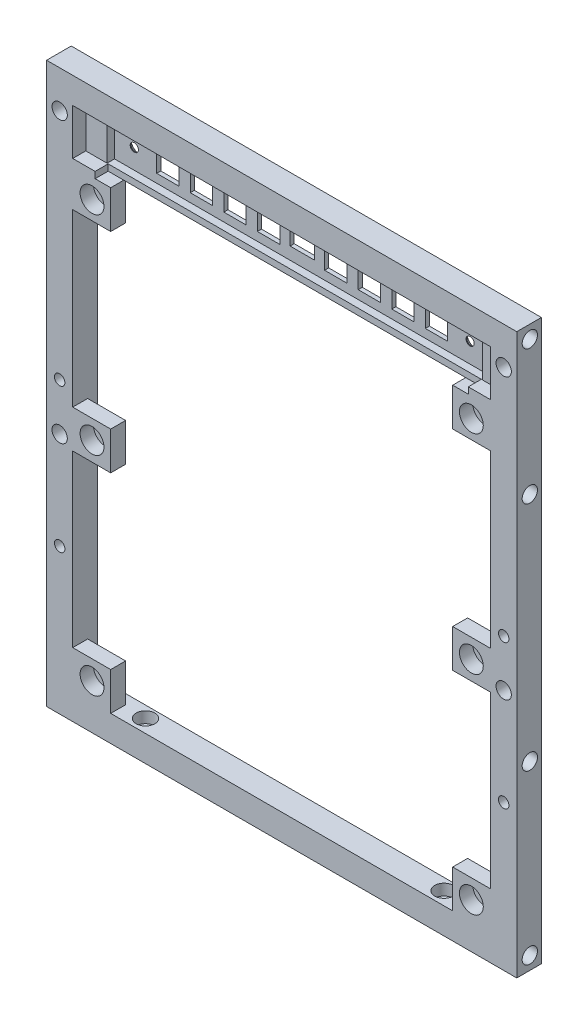
SolidWorks part; units mm, degrees
ref_plane "Front Plane" through (0, 0, 0) normal (0, 0, 1) x (1, 0, 0)
ref_plane "Top Plane" through (0, 0, 0) normal (0, 1, 0) x (1, 0, 0)
ref_plane "Right Plane" through (0, 0, 0) normal (1, 0, 0) x (0, 0, -1)
sketch "Sketch1" plane through (0, 0, 0) normal (0, 0, 1) x (1, 0, 0)
  line L1 (-63, -75) -> (63, -75)
  line L2 (-63, -75) -> (-63, 75)
  line L3 (-63, 75) -> (63, 75)
  line L4 (63, -75) -> (63, 75)
  line L5 (-63, -75) -> (63, 75) construction
  line L6 (-63, 75) -> (63, -75) construction
  line L7 (-56, -68) -> (56, -68)
  line L8 (-56, -68) -> (-56, 68)
  line L9 (-56, 68) -> (56, 68)
  line L10 (56, -68) -> (56, 68)
  line L11 (-56, -68) -> (56, 68) construction
  line L12 (-56, 68) -> (56, -68) construction
  point P0 (0, 0)
  point P6 (0, 0)
  dimension "D1" = 126
  dimension "D2" = 150
  dimension "D3" = 7
  dimension "D4" = 7
extrude "Boss-Extrude1" add sketch "Sketch1" along normal blind 7
sketch "Sketch2" plane through (-63, 0, 0) normal (-1, 0, 0) x (0, 0, 1)
  line L0 (3.5, 71.5) -> (3.5, -71.5) construction
  line L1 (7, 75) -> (0, 75) construction
  circle A0 centre (3.5, -71.5) radius 2.05
  circle A2 centre (3.5, 71.5) radius 2.05
  circle A3 centre (3.5, 35.5) radius 2.05
  circle A4 centre (3.5, -26.5) radius 2.05
  point P2 (3.5, 0)
  point P7 (3.5, 75)
  dimension "D2" = 4.1
  dimension "D3" = 36
  dimension "D4" = 45
  dimension "D1" = 3.5
extrude "Cut-Extrude1" cut sketch "Sketch2" against normal blind 6
mirror "Mirror1" about plane through (0, 0, 0) normal (1, 0, 0) of "Cut-Extrude1"
sketch "Sketch3" plane through (0, -68, 0) normal (0, 1, 0) x (1, 0, 0)
  line L0 (0, 0) -> (0, -7) construction
  line L1 (-56, 0) -> (56, 0) construction
  line L2 (-56, -7) -> (56, -7) construction
  line L3 (40, -3.5) -> (-40, -3.5) construction
  circle A0 centre (40, -3.5) radius 1.35
  circle A1 centre (-40, -3.5) radius 1.35
  point P9 (0, -3.5)
  dimension "D1" = 2.7
  dimension "D2" = 80
extrude "Cut-Extrude2" cut sketch "Sketch3" against normal through all
sketch "Sketch4" plane through (0, -68, 0) normal (0, 1, 0) x (1, 0, 0)
  circle A0 centre (40, -3.5) radius 2.5
  circle A1 centre (-40, -3.5) radius 2.5
  dimension "D1" = 5
extrude "Cut-Extrude3" cut sketch "Sketch4" against normal blind 3
sketch "Sketch5" plane through (0, 0, 0) normal (0, 0, -1) x (-1, 0, 0)
  line L0 (-59.5, -75) -> (-59.5, 75) construction
  line L1 (63, -75) -> (-63, -75) construction
  line L2 (-63, 75) -> (63, 75) construction
  line L3 (-56, 0) -> (-63, 0) construction
  line L4 (-56, -68) -> (-56, 68) construction
  line L5 (-63, -75) -> (-63, 75) construction
  line L6 (0, 75) -> (0, -75) construction
  line L7 (56, -68) -> (-56, -68) construction
  circle A0 centre (-59.5, 2.6) radius 1.4
  circle A1 centre (59.5, 2.6) radius 1.4
  circle A2 centre (-59.5, -36) radius 1.4
  circle A3 centre (59.5, -36) radius 1.4
  point P12 (-59.5, 0)
  point P13 (-59.5, 0)
  dimension "D1" = 2.8
  dimension "D2" = 2.6
  dimension "D3" = 32
extrude "Cut-Extrude4" cut sketch "Sketch5" against normal through all
sketch "Sketch6" plane through (0, 0, 0) normal (0, 0, -1) x (-1, 0, 0)
  circle A0 centre (-59.5, 2.6) radius 2.5
  circle A1 centre (59.5, 2.6) radius 2.5
  circle A2 centre (-59.5, -36) radius 2.5
  circle A3 centre (59.5, -36) radius 2.5
  dimension "D1" = 5
extrude "Cut-Extrude5" cut sketch "Sketch6" against normal blind 3
sketch "Sketch7" plane through (0, 0, 0) normal (0, 0, -1) x (-1, 0, 0)
  line L0 (-56, 68) -> (-63, 68) construction
  line L1 (-63, -75) -> (-63, 75) construction
  line L2 (-59.5, 65) -> (-59.5, -10) construction
  line L3 (-63, 75) -> (63, 75) construction
  circle A0 centre (-59.5, 65) radius 2.05
  circle A1 centre (-59.5, -10) radius 2.05
  point P8 (-59.5, 68)
  dimension "D1" = 4.1
  dimension "D2" = 10
  dimension "D3" = 75
extrude "Cut-Extrude6" cut sketch "Sketch7" against normal through all
mirror "Mirror2" about plane through (0, 0, 0) normal (1, 0, 0) of "Cut-Extrude6"
sketch "Sketch8" plane through (0, 0, 3) normal (0, 0, -1) x (-1, 0, 0)
  line L2 (-60.9, 0.5288) -> (-60.9, 4.6712)
  line L4 (-58.1, 0.5288) -> (-58.1, 4.6712)
  line L5 (-60.9, 0.5288) -> (-58.1, 4.6712) construction
  line L6 (-60.9, 4.6712) -> (-58.1, 0.5288) construction
  line L8 (-60.9, -38.0712) -> (-60.9, -33.9288)
  line L10 (-58.1, -38.0712) -> (-58.1, -33.9288)
  line L11 (-60.9, -38.0712) -> (-58.1, -33.9288) construction
  line L12 (-60.9, -33.9288) -> (-58.1, -38.0712) construction
  circle A0 centre (-59.5, 2.6) radius 2.5 construction
  circle A1 centre (-59.5, -36) radius 2.5 construction
  circle A2 centre (-59.5, -36) radius 2.5 construction
  arc A3 (-58.1, 4.6712) -> (-60.9, 4.6712) centre (-59.5, 2.6) ccw
  arc A4 (-58.1, -33.9288) -> (-60.9, -33.9288) centre (-59.5, -36) ccw
  circle A5 centre (-59.5, 2.6) radius 1.4 construction
  circle A6 centre (-59.5, -36) radius 1.4 construction
  arc A7 (-60.9, -38.0712) -> (-58.1, -38.0712) centre (-59.5, -36) ccw
  arc A8 (-60.9, 0.5288) -> (-58.1, 0.5288) centre (-59.5, 2.6) ccw
  point P0 (-59.5, 2.6)
  point P8 (-59.5, -36)
extrude "Cut-Extrude7" cut sketch "Sketch8" against normal blind 0.2
sketch "Sketch9" plane through (0, 0, 3.2) normal (0, 0, -1) x (-1, 0, 0)
  line L0 (-58.1, 2.6) -> (-58.1, 4.6712) construction
  line L1 (-60.9, 1.2) -> (-58.1, 1.2)
  line L2 (-60.9, 1.2) -> (-60.9, 4)
  line L3 (-60.9, 4) -> (-58.1, 4)
  line L4 (-58.1, 1.2) -> (-58.1, 4)
  line L5 (-60.9, 1.2) -> (-58.1, 4) construction
  line L6 (-60.9, 4) -> (-58.1, 1.2) construction
  line L7 (-58.1, -38.0712) -> (-58.1, -33.9288) construction
  line L8 (-60.9, -37.4) -> (-58.1, -37.4)
  line L9 (-60.9, -37.4) -> (-60.9, -34.6)
  line L10 (-60.9, -34.6) -> (-58.1, -34.6)
  line L11 (-58.1, -37.4) -> (-58.1, -34.6)
  line L12 (-60.9, -37.4) -> (-58.1, -34.6) construction
  line L13 (-60.9, -34.6) -> (-58.1, -37.4) construction
  arc A0 (-58.1, 2.6) -> (-60.9, 2.6) centre (-59.5, 2.6) ccw construction
  point P0 (-59.5, 2.6)
  point P8 (-59.5, -36)
extrude "Cut-Extrude8" cut sketch "Sketch9" against normal blind 0.2
mirror "Mirror3" about plane through (0, 0, 0) normal (1, 0, 0) of "Cut-Extrude8", "Cut-Extrude7"
sketch "Sketch10" plane through (0, 0, 7) normal (0, 0, 1) x (1, 0, 0)
  line L0 (56, -68) -> (56, 68) construction
  line L1 (56, -68) -> (50, -68)
  line L2 (56, -68) -> (56, -62)
  line L3 (56, -62) -> (50, -62)
  line L4 (50, -68) -> (50, -62)
  line L5 (56, -38.5) -> (50, -38.5)
  line L6 (56, -38.5) -> (56, -32.5)
  line L7 (56, -32.5) -> (50, -32.5)
  line L8 (50, -38.5) -> (50, -32.5)
  line L9 (-56, -68) -> (56, -68) construction
  dimension "D1" = 6
  dimension "D2" = 35.5
extrude "Boss-Extrude2" add sketch "Sketch10" against normal offset from surface (5.5 mm away) 1.5 up to face at (-57.45, -10, 0)
sketch "Sketch11" plane through (0, 0, 1.5) normal (0, 0, -1) x (-1, 0, 0)
  line L0 (-56, -38.5) -> (-50, -32.5) construction
  line L2 (-56, -68) -> (-50, -62) construction
  circle A0 centre (-53, -35.5) radius 1.65
  circle A1 centre (-53, -65) radius 1.65
  dimension "D1" = 3.3
extrude "Cut-Extrude9" cut sketch "Sketch11" against normal through all
mirror "Mirror4" about plane through (0, 0, 0) normal (1, 0, 0) of "Cut-Extrude9", "Boss-Extrude2"
sketch "Sketch12" plane through (0, 0, 0) normal (0, 0, -1) x (-1, 0, 0)
  line L0 (56, 68) -> (56, -68) construction
  line L1 (-56, 68) -> (56, 68)
  line L2 (-56, 68) -> (-56, 54)
  line L3 (-56, 54) -> (56, 54)
  line L4 (56, 68) -> (56, 54)
  dimension "D1" = 14
extrude "Boss-Extrude3" add sketch "Sketch12" against normal blind 1.5
sketch "Sketch13" plane through (0, 0, 1.5) normal (0, 0, 1) x (1, 0, 0)
  line L0 (-56, 68) -> (56, 54) construction
  line L2 (-50.3, 55.7) -> (50.3, 55.7)
  line L3 (-50.3, 55.7) -> (-50.3, 66.3)
  line L4 (-50.3, 66.3) -> (50.3, 66.3)
  line L5 (50.3, 55.7) -> (50.3, 66.3)
  line L6 (-50.3, 55.7) -> (50.3, 66.3) construction
  line L7 (-50.3, 66.3) -> (50.3, 55.7) construction
  line L8 (-56, 54) -> (56, 54)
  line L9 (-56, 54) -> (-56, 68)
  line L10 (-56, 68) -> (56, 68)
  line L11 (56, 54) -> (56, 68)
  line L12 (-56, 54) -> (56, 68) construction
  line L13 (-56, 68) -> (56, 54) construction
  point P4 (0, 61)
  point P9 (0, 61)
  dimension "D1" = 100.6
  dimension "D2" = 10.6
extrude "Boss-Extrude4" add sketch "Sketch13" along normal blind 2
sketch "Sketch14" plane through (0, 0, 1.5) normal (0, 0, 1) x (1, 0, 0)
  line L0 (0, 66.3) -> (0, 55.7) construction
  line L1 (50.3, 66.3) -> (-50.3, 66.3) construction
  line L2 (-50.3, 55.7) -> (50.3, 55.7) construction
  line L3 (-50.3, 61) -> (50.3, 61) construction
  line L4 (50.3, 55.7) -> (50.3, 66.3) construction
  line L5 (-33, 64) -> (-39, 64)
  line L6 (-3.25, 59) -> (3.25, 59)
  line L7 (-3.25, 59) -> (-3.25, 63)
  line L8 (-3.25, 63) -> (3.25, 63)
  line L9 (3.25, 59) -> (3.25, 63)
  line L10 (-3.25, 59) -> (3.25, 63) construction
  line L11 (-3.25, 63) -> (3.25, 59) construction
  line L12 (6, 58) -> (12, 58)
  line L13 (6, 58) -> (6, 64)
  line L14 (6, 64) -> (12, 64)
  line L15 (12, 58) -> (12, 64)
  line L16 (6, 58) -> (12, 64) construction
  line L17 (6, 64) -> (12, 58) construction
  line L18 (15, 58) -> (21, 58)
  line L19 (15, 58) -> (15, 64)
  line L20 (15, 64) -> (21, 64)
  line L21 (21, 58) -> (21, 64)
  line L22 (15, 58) -> (21, 64) construction
  line L23 (15, 64) -> (21, 58) construction
  line L24 (24, 58) -> (30, 58)
  line L25 (24, 58) -> (24, 64)
  line L26 (24, 64) -> (30, 64)
  line L27 (30, 58) -> (30, 64)
  line L28 (24, 58) -> (30, 64) construction
  line L29 (24, 64) -> (30, 58) construction
  line L30 (33, 58) -> (39, 58)
  line L31 (33, 58) -> (33, 64)
  line L32 (33, 64) -> (39, 64)
  line L33 (39, 58) -> (39, 64)
  line L34 (33, 58) -> (39, 64) construction
  line L35 (33, 64) -> (39, 58) construction
  line L36 (-39, 58) -> (-39, 64)
  line L37 (-33, 58) -> (-39, 58)
  line L38 (-33, 58) -> (-33, 64)
  line L39 (-24, 64) -> (-30, 64)
  line L40 (-30, 58) -> (-30, 64)
  line L41 (-24, 58) -> (-30, 58)
  line L42 (-24, 58) -> (-24, 64)
  line L43 (-15, 64) -> (-21, 64)
  line L44 (-21, 58) -> (-21, 64)
  line L45 (-15, 58) -> (-21, 58)
  line L46 (-15, 58) -> (-15, 64)
  line L47 (-6, 64) -> (-12, 64)
  line L48 (-12, 58) -> (-12, 64)
  line L49 (-6, 58) -> (-12, 58)
  line L50 (-6, 58) -> (-6, 64)
  circle A0 centre (-45, 61) radius 1.3 construction
  circle A1 centre (45, 61) radius 1.3 construction
  point P6 (0, 61)
  point P11 (0, 61)
  point P16 (9, 61)
  point P21 (18, 61)
  point P26 (27, 61)
  point P31 (36, 61)
  dimension "D10" = 2.6
  dimension "D9" = 45
  dimension "D1" = 6.5
  dimension "D2" = 4
  dimension "D3" = 6
  dimension "D4" = 9
  dimension "D5" = 9
  dimension "D6" = 9
  dimension "D7" = 9
  dimension "D8" = 45
extrude "Cut-Extrude10" cut sketch "Sketch14" against normal through all
sketch "Sketch15" plane through (0, 0, 1.5) normal (0, 0, 1) x (1, 0, 0)
  circle A0 centre (-45, 61) radius 1
  circle A1 centre (45, 61) radius 1
  dimension "D1" = 2
extrude "Boss-Extrude5" add sketch "Sketch15" along normal up to surface (2 mm away) up to face at (0, 61, 3.5)
chamfer "Chamfer1" distance 0.4 angle 45 3 edges at (-56, -7, 0) (56, -7, 0) (0, -68, 0) tangent propagation no
chamfer "Chamfer2" distance 0.4 angle 45 4 edges at (0, 75, 0) (-63, 0, 0) (0, -75, 0) (63, 0, 0)
chamfer "Chamfer3" distance 0.4 angle 45 36 edges at (-36, 58, 0) (-39, 61, 0) (-36, 64, 0) (-33, 61, 0) (-27, 58, 0) (-30, 61, 0) (-27, 64, 0) (-24, 61, 0) (-18, 58, 0) (-21, 61, 0) (-18, 64, 0) (-15, 61, 0) (-9, 58, 0) (-12, 61, 0) (-9, 64, 0) (-6, 61, 0) (0, 59, 0) (-3.25, 61, 0) (0, 63, 0) (3.25, 61, 0) (9, 58, 0) (6, 61, 0) (9, 64, 0) (12, 61, 0) (18, 58, 0) (15, 61, 0) (18, 64, 0) (21, 61, 0) (36, 58, 0) (33, 61, 0) (36, 64, 0) (39, 61, 0) (27, 58, 0) (24, 61, 0) (27, 64, 0) (30, 61, 0)
sketch "Sketch16" plane through (0, 0, 7) normal (0, 0, 1) x (1, 0, 0)
  line L0 (-50, 54) -> (-50, 55.7)
  line L1 (-56, -32.5) -> (-50, -32.5)
  line L2 (-56, -32.5) -> (-56, -26.5)
  line L3 (-56, -26.5) -> (-50, -26.5)
  line L4 (-50, -32.5) -> (-50, -26.5)
  line L5 (56, -32.5) -> (50, -32.5)
  line L6 (56, -32.5) -> (56, -26.5)
  line L7 (56, -26.5) -> (50, -26.5)
  line L8 (50, -32.5) -> (50, -26.5)
  line L9 (56, 54) -> (50, 54) construction
  line L10 (56, 54) -> (56, 48)
  line L11 (56, 48) -> (50, 48)
  line L12 (50, 54) -> (50, 48)
  line L13 (-56, 54) -> (-50, 54) construction
  line L14 (-56, 54) -> (-56, 48)
  line L15 (-56, 48) -> (-50, 48)
  line L16 (-50, 54) -> (-50, 48)
  line L17 (-50.3, 55.7) -> (50.3, 55.7) construction
  line L18 (-50, 55.7) -> (-56, 55.7)
  line L19 (-56, 68) -> (-56, 54) construction
  line L20 (-56, 55.7) -> (-56, 54)
  line L21 (50, 54) -> (50, 55.7)
  line L22 (50, 55.7) -> (56, 55.7)
  line L23 (56, 54) -> (56, 68) construction
  line L24 (56, 55.7) -> (56, 54)
  dimension "D1" = 6
extrude "Boss-Extrude7" add sketch "Sketch16" against normal offset from surface (5.5 mm away) 1.5 up to face at (-36, 61, 0)
sketch "Sketch17" plane through (0, 0, 1.5) normal (0, 0, -1) x (-1, 0, 0)
  line L0 (-50, 48) -> (50, -26.5) construction
  line L1 (-50, -26.5) -> (-50, -38.5) construction
  line L2 (-53, -29.5) -> (53, -29.5) construction
  line L3 (-53, -29.5) -> (-53, 51) construction
  line L4 (-53, 51) -> (53, 51) construction
  line L5 (53, -29.5) -> (53, 51) construction
  line L6 (-53, -29.5) -> (53, 51) construction
  line L7 (-53, 51) -> (53, -29.5) construction
  line L8 (50, -26.5) -> (56, -26.5) construction
  circle A0 centre (-53, -29.5) radius 1.65
  circle A1 centre (53, -29.5) radius 1.65
  circle A2 centre (53, 51) radius 1.65
  circle A3 centre (-53, 51) radius 1.65
  point P4 (0, 10.75)
  dimension "D3" = 3.3
  dimension "D1" = 3
  dimension "D2" = 3
extrude "Cut-Extrude11" cut sketch "Sketch17" against normal through all
sketch "Sketch18" plane through (0, 0, 1.5) normal (0, 0, 1) x (1, 0, 0)
  circle A0 centre (-45, 61) radius 1.1
  circle A1 centre (45, 61) radius 1.1
  dimension "D1" = 2.2
extrude "Cut-Extrude12" cut sketch "Sketch18" against normal through all both and the other way through all
chamfer "Chamfer4" distance 1.3 angle 45 2 edges at (-43.9, 61, 0) (46.1, 61, 0)
sketch "Sketch19" plane through (0, 0, 1.5) normal (0, 0, -1) x (-1, 0, 0)
  line L1 (-56, -68) -> (56, -68)
  line L2 (-56, -68) -> (-56, 54)
  line L3 (-56, 54) -> (56, 54)
  line L4 (56, -68) -> (56, 54)
extrude "Cut-Extrude13" cut sketch "Sketch19" against normal through all
ref_plane "Plane1" through (0, 0, 3) normal (0, 0, 1) x (1, 0, 0)
sketch "Sketch20" plane through (0, 0, 3) normal (0, 0, 1) x (1, 0, 0)
  line L0 (56, 54) -> (56, -68) construction
  line L1 (56, -68) -> (48, -68)
  line L2 (56, -68) -> (56, -60)
  line L3 (56, -60) -> (48, -60)
  line L4 (48, -68) -> (48, -60)
  line L5 (56, 54) -> (48, 54)
  line L6 (56, 54) -> (56, 46)
  line L7 (56, 46) -> (48, 46)
  line L8 (48, 54) -> (48, 46)
  line L9 (56, -24.5) -> (48, -24.5)
  line L10 (56, -24.5) -> (56, -32.5)
  line L11 (56, -32.5) -> (48, -32.5)
  line L12 (48, -24.5) -> (48, -32.5)
  dimension "D1" = 8
  dimension "D2" = 27.5
extrude "Boss-Extrude8" add sketch "Sketch20" along normal blind 7
sketch "Sketch21" plane through (0, 0, 3) normal (0, 0, -1) x (-1, 0, 0)
  line L0 (-48, 54) -> (-56, 46) construction
  line L1 (-56, -60) -> (-48, -68) construction
  line L2 (-56, -24.5) -> (-48, -32.5) construction
  circle A0 centre (-52, 50) radius 2.1
  circle A1 centre (-52, -64) radius 2.1
  circle A2 centre (-52, -28.5) radius 2.1
  dimension "D1" = 4.2
extrude "Cut-Extrude14" cut sketch "Sketch21" against normal through all
mirror "Mirror5" about plane through (0, 0, 0) normal (1, 0, 0) of "Cut-Extrude14", "Boss-Extrude8"
chamfer "Chamfer5" distance 3 angle 45 6 edges at (-56, -64, 7) (56, -64, 7) (56, 50, 7) (-56, 50, 7) (-56, -28.5, 7) (56, -28.5, 7)
sketch "Sketch22" plane through (0, 0, 3) normal (0, 0, -1) x (-1, 0, 0)
  line L1 (-56, 54) -> (56, 54)
  line L2 (-56, 54) -> (-56, -68)
  line L3 (-56, -68) -> (56, -68)
  line L4 (56, 54) -> (56, -68)
extrude "Cut-Extrude15" cut sketch "Sketch22" against normal blind 10
sketch "Sketch23" plane through (-56, 0, 0) normal (1, 0, 0) x (0, 0, -1)
  line L1 (-7, 54) -> (-10, 54)
  line L2 (-7, 54) -> (-7, -68)
  line L3 (-7, -68) -> (-10, -68)
  line L4 (-10, 54) -> (-10, -68)
extrude "Cut-Extrude16" cut sketch "Sketch23" against normal through all both and the other way through all
sketch "Sketch24" plane through (0, 0, 0) normal (0, 0, -1) x (-1, 0, 0)
  circle A0 centre (-50.825, 48.75) radius 3.2 construction
  circle A1 centre (-50.825, -62.95) radius 3.2 construction
  circle A4 centre (50.825, -7.1) radius 3.2 construction
  circle A6 centre (-50.825, 48.75) radius 3.2
  circle A7 centre (-50.825, -62.95) radius 3.2
  circle A8 centre (-50.825, -7.1) radius 3.2
  circle A9 centre (50.825, -62.95) radius 3.2
  circle A10 centre (50.825, -7.1) radius 3.2
  circle A11 centre (50.825, 48.75) radius 3.2
  point P5 (0, 0)
  point P7 (0, 0)
  point P11 (0, 0)
  point P18 (0, 0)
  point P19 (0, 0)
  point P20 (0, 0)
sketch "Sketch25" plane through (0, 0, 3) normal (0, 0, 1) x (1, 0, 0)
  line L0 (-56, 54) -> (-56, -68) construction
  line L1 (-56, 54) -> (-45.825, 54)
  line L2 (-56, 54) -> (-56, 43.825)
  line L3 (-56, 43.825) -> (-45.825, 43.825)
  line L4 (-45.825, 54) -> (-45.825, 43.825)
  line L5 (-56, -2.0125) -> (-45.825, -2.0125)
  line L6 (-56, -2.0125) -> (-56, -12.1875)
  line L7 (-56, -12.1875) -> (-45.825, -12.1875)
  line L8 (-45.825, -2.0125) -> (-45.825, -12.1875)
  line L9 (0, 54) -> (0, -68) construction
  line L10 (-56, -68) -> (-45.825, -68)
  line L11 (-56, -68) -> (-56, -57.825)
  line L12 (-56, -57.825) -> (-45.825, -57.825)
  line L13 (-45.825, -68) -> (-45.825, -57.825)
  line L14 (-50, 54) -> (50, 54) construction
  line L15 (-56, -68) -> (56, -68) construction
  line L16 (45.825, -68) -> (45.825, -57.825)
  line L17 (56, -57.825) -> (45.825, -57.825)
  line L18 (56, -68) -> (56, -57.825)
  line L19 (56, -68) -> (45.825, -68)
  line L20 (45.825, -2.0125) -> (45.825, -12.1875)
  line L21 (56, -12.1875) -> (45.825, -12.1875)
  line L22 (56, -2.0125) -> (56, -12.1875)
  line L23 (56, -2.0125) -> (45.825, -2.0125)
  line L24 (45.825, 54) -> (45.825, 43.825)
  line L25 (56, 43.825) -> (45.825, 43.825)
  line L26 (56, 54) -> (56, 43.825)
  line L27 (56, 54) -> (45.825, 54)
  point P16 (-45.825, -7.1)
  dimension "D1" = 5
extrude "Boss-Extrude9" add sketch "Sketch25" along normal up to surface (4 mm away) up to face at (0, 0, 7)
sketch "Sketch26" plane through (0, 0, 7) normal (0, 0, 1) x (1, 0, 0)
  circle A0 centre (-50.825, -7.1) radius 3.2 construction
  circle A1 centre (-50.825, -62.95) radius 3.2 construction
  circle A2 centre (50.825, -62.95) radius 3.2 construction
  circle A3 centre (50.825, -7.1) radius 3.2 construction
  circle A4 centre (50.825, 48.75) radius 3.2 construction
  circle A5 centre (-50.825, 48.75) radius 3.2 construction
  circle A6 centre (-50.825, -7.1) radius 3.2
  circle A7 centre (-50.825, -62.95) radius 3.2
  circle A8 centre (50.825, -62.95) radius 3.2
  circle A9 centre (50.825, -7.1) radius 3.2
  circle A10 centre (50.825, 48.75) radius 3.2
  circle A11 centre (-50.825, 48.75) radius 3.2
extrude "Cut-Extrude17" cut sketch "Sketch26" against normal offset from surface (3.6 mm away) 0.4 up to face at (-50.9125, 48.9125, 3)
